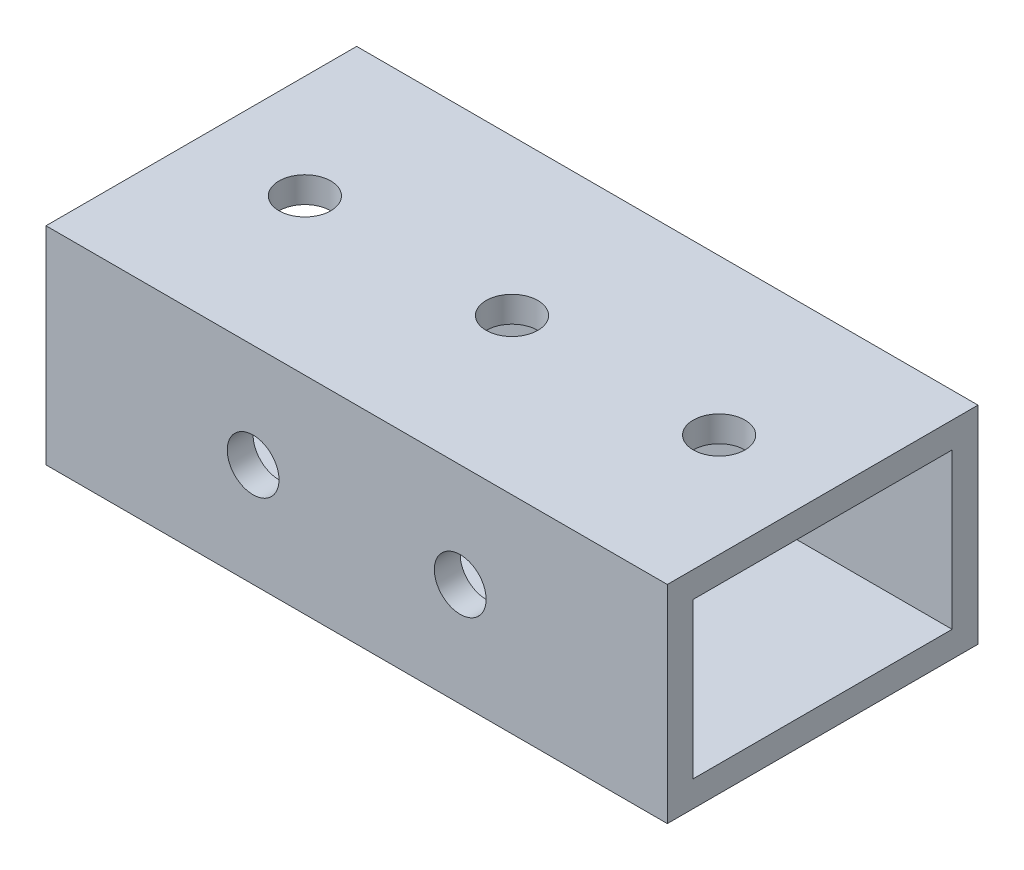
SolidWorks part; units mm, degrees
material "6061-T6 (SS)"
ref_plane "Front Plane" through (0, 0, 0) normal (0, 0, 1) x (1, 0, 0)
ref_plane "Top Plane" through (0, 0, 0) normal (0, 1, 0) x (1, 0, 0)
ref_plane "Right Plane" through (0, 0, 0) normal (1, 0, 0) x (0, 0, -1)
sketch "Sketch1" plane through (0, 0, 0) normal (0, 1, 0) x (1, 0, 0)
  line L1 (-38.1, -19.05) -> (38.1, -19.05)
  line L2 (-38.1, -19.05) -> (-38.1, 19.05)
  line L3 (-38.1, 19.05) -> (38.1, 19.05)
  line L4 (38.1, -19.05) -> (38.1, 19.05)
  line L5 (-38.1, -19.05) -> (38.1, 19.05) construction
  line L6 (-38.1, 19.05) -> (38.1, -19.05) construction
  point P1 (0, 0)
extrude "Boss-Extrude1" add sketch "Sketch1" along normal blind 25.4
sketch "Sketch2" plane through (38.1, 0, 0) normal (1, 0, 0) x (0, 0, -1)
  line L0 (0, 0) -> (0, 25.4) construction
  line L1 (-19.05, 0) -> (19.05, 0) construction
  line L2 (-19.05, 25.4) -> (19.05, 25.4) construction
  line L4 (-15.875, 22.225) -> (15.875, 22.225)
  line L5 (-15.875, 22.225) -> (-15.875, 3.175)
  line L6 (-15.875, 3.175) -> (15.875, 3.175)
  line L7 (15.875, 22.225) -> (15.875, 3.175)
  line L8 (-15.875, 22.225) -> (15.875, 3.175) construction
  line L9 (-15.875, 3.175) -> (15.875, 22.225) construction
  point P6 (0, 12.7)
extrude "Cut-Extrude1" cut sketch "Sketch2" against normal blind 127
sketch "Sketch3" plane through (0, 25.4, 0) normal (0, 1, 0) x (1, 0, 0)
  line L0 (-38.1, 0) -> (38.1, 0) construction
  line L1 (-38.1, 19.05) -> (-38.1, -19.05) construction
  line L2 (38.1, -19.05) -> (38.1, 19.05) construction
  circle A0 centre (-25.4, 0) radius 3.175
  circle A1 centre (0, 0) radius 3.175
  circle A2 centre (25.4, 0) radius 3.175
  dimension "D1" = 12.7
  dimension "D2" = 12.7
ref_plane "Plane1" through (0, 12.7, 0) normal (0, 1, 0) x (1, 0, 0)
extrude "Cut-Extrude2" cut sketch "Sketch3" against normal blind 3.175 contours A0 | A1
mirror "Mirror1" about plane through (0, 12.7, 0) normal (0, 1, 0) of "Cut-Extrude2"
sketch "Sketch4" plane through (0, 0, 19.05) normal (0, 0, 1) x (1, 0, 0)
  line L0 (-38.1, 12.7) -> (38.1, 12.7) construction
  line L1 (-38.1, 25.4) -> (-38.1, 0) construction
  line L2 (38.1, 25.4) -> (38.1, 0) construction
  circle A0 centre (-12.7, 12.7) radius 3.175
  circle A1 centre (12.7, 12.7) radius 3.175
  dimension "D1" = 25.4
  dimension "D2" = 25.4
extrude "Cut-Extrude4" cut sketch "Sketch4" against normal blind 3.175
mirror "Mirror3" about plane through (0, 0, 0) normal (0, 0, 1) of "Cut-Extrude4"
extrude "Cut-Extrude5" cut sketch "Sketch3<5>" against normal blind 3.175 contours A2
sketch "Sketch3<5>" plane through (0, 25.4, 0) normal (0, 1, 0) x (1, 0, 0) same geometry as "Sketch3"
